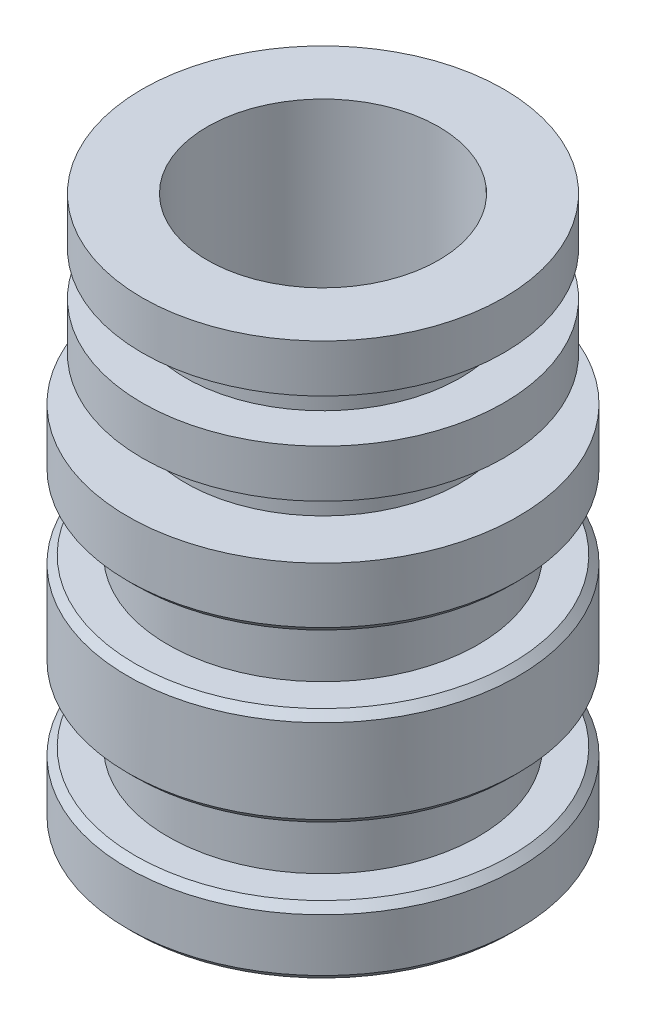
SolidWorks part; units mm, degrees
material "AISI 316 Barre d'acier inoxydable recuit (SS)"
ref_plane "Plan de face" through (0, 0, 0) normal (0, 0, 1) x (1, 0, 0)
ref_plane "Plan de dessus" through (0, 0, 0) normal (0, 1, 0) x (1, 0, 0)
ref_plane "Plan de droite" through (0, 0, 0) normal (1, 0, 0) x (0, 0, -1)
sketch "Esquisse1" plane through (0, 0, 0) normal (0, 0, 1) x (1, 0, 0)
  line L0 (0, -29.1154) -> (0, 30.7029) construction
  line L4 (-2, 14.84) -> (-2, -6.16) construction
  line L5 (-2, -6.16) -> (0, -6.16) construction
  line L9 (0, 0) -> (-13.5, 0)
  line L10 (-13.5, 0) -> (-13.5, 25.2) construction
  line L11 (-2, 14.84) -> (-8, 20.84) construction
  line L13 (-12.5, 29.0574) -> (-12.5, 31.5) construction
  line L18 (-12.5, 31.5) -> (-12.5, 28.2)
  line L19 (-12.5, 28.2) -> (-9.5, 28.2)
  line L20 (-9.5, 28.2) -> (-9.5, 25.2)
  line L29 (-9.5, 25.2) -> (-12.5, 25.2)
  line L33 (-13.5, 25.2) -> (-12.5, 25.2)
  line L35 (-13.5, 25.2) -> (-13.5, 20.84)
  line L36 (-13.5, 16.14) -> (-13.5, 9.34)
  line L37 (-13.5, 4.64) -> (-13.5, 0)
  line L39 (-2, 14.84) -> (-2, -6.16) construction
  line L42 (-8, 20.84) -> (-8, 8)
  line L43 (-8, 8) -> (0, 8)
  line L44 (-13.5, 20.84) -> (-10.73, 20.84)
  line L45 (-10.73, 20.84) -> (-10.73, 16.14)
  line L46 (-10.73, 16.14) -> (-13.5, 16.14)
  line L47 (-13.5, 9.34) -> (-10.73, 9.34)
  line L48 (-10.73, 9.34) -> (-10.73, 4.64)
  line L49 (-10.73, 4.64) -> (-13.5, 4.64)
  line L50 (0, 8) -> (0, 0)
  line L51 (-12.5, 31.5) -> (-9.5, 31.5)
  line L52 (-9.5, 31.5) -> (-9.5, 34.5)
  line L53 (-9.5, 34.5) -> (-12.5, 34.5)
  line L54 (-12.5, 34.5) -> (-12.5, 37.8)
  line L55 (-12.5, 37.8) -> (-8, 37.8)
  line L56 (-8, 37.8) -> (-8, 20.84)
  point P3 (-13, 25.2)
  dimension "D5" = 4.7
  dimension "D12" = 25.2
  dimension "D7" = 10.73
  dimension "D1" = 2
  dimension "D2" = 13.5
  dimension "D3" = 8
  dimension "D4" = 1
  dimension "D6" = 6.8
  dimension "D8" = 4.36
  dimension "D9" = 4.64
  dimension "D10" = 3
  dimension "45" = 45
  dimension "D11" = 8
  dimension "D13" = 21
  dimension "D14" = 9.5
  dimension "D15" = 3
  dimension "D16" = 12.5
  dimension "D17" = 3.3
revolve "Révolution1" add sketch "Esquisse1" angle 360 about L0
sketch "Esquisse4" plane through (0, 0, 0) normal (0, -1, 0) x (1, 0, 0)
  circle A0 centre (0, 0) radius 4
  dimension "D1" = 8
extrude "Enlèv. mat.-Extru.3" cut sketch "Esquisse4" against normal through all
chamfer "Chanfrein4" distance 0.5 angle 45 2 edges at (0, 8, -4) (0, 0, -4)
chamfer "Chanfrein3" distance 0.5 angle 45 5 edges at (0, 0, -13.5) (0, 20.84, -13.5) (0, 16.14, -13.5) (0, 9.34, -13.5) (0, 4.64, -13.5)
equation "\"1à.00mm\"=12"
